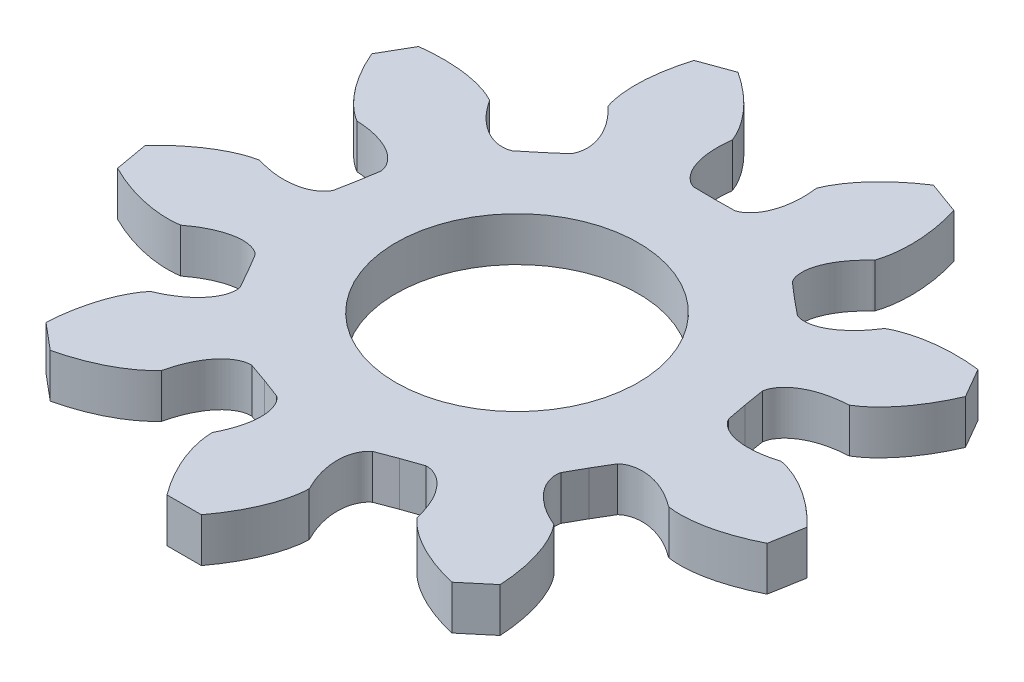
SolidWorks part; units mm, degrees
ref_plane "Plano frontal" through (0, 0, 0) normal (0, 0, 1) x (1, 0, 0)
ref_plane "Plano superior" through (0, 0, 0) normal (0, 1, 0) x (1, 0, 0)
ref_plane "Plano direito" through (0, 0, 0) normal (1, 0, 0) x (0, 0, -1)
sketch "Esboço1" plane through (0, 0, 0) normal (0, 1, 0) x (1, 0, 0)
  line L0 (-25.3837, 16.4538) -> (-26.9413, 13.7561)
  line L1 (-30.0214, -3.712) -> (-29.4805, -6.7798)
  line L2 (-16.4467, -7.3117) -> (-15.4802, -8.9375)
  line L3 (-15.4802, -8.9375) -> (-14.5555, -10.5874)
  line L4 (-17.2988, 4.9706) -> (-17.6034, 3.104)
  line L5 (-17.6034, 3.104) -> (-17.9556, 1.2457)
  line L6 (-8.8688, 28.9207) -> (-11.796, 27.8553)
  line L7 (-10.0566, 14.9272) -> (-11.4898, 13.693)
  line L8 (-11.4898, 13.693) -> (-12.9541, 12.4959)
  line L9 (11.796, 27.8553) -> (8.8688, 28.9207)
  line L10 (1.8912, 17.8991) -> (0, 17.875)
  line L11 (0, 17.875) -> (-1.8912, 17.8991)
  line L12 (26.9413, 13.7561) -> (25.3837, 16.4538)
  line L13 (12.9541, 12.4959) -> (11.4898, 13.693)
  line L14 (11.4898, 13.693) -> (10.0566, 14.9272)
  line L15 (29.4805, -6.7798) -> (30.0214, -3.712)
  line L16 (17.9556, 1.2457) -> (17.6034, 3.104)
  line L17 (17.6034, 3.104) -> (17.2988, 4.9706)
  line L18 (18.2254, -24.1433) -> (20.6117, -22.1409)
  line L19 (14.5555, -10.5874) -> (15.4802, -8.9375)
  line L20 (15.4802, -8.9375) -> (16.4467, -7.3117)
  line L21 (-1.5575, -30.2099) -> (1.5575, -30.2099)
  line L22 (4.3447, -17.4665) -> (6.1136, -16.797)
  line L23 (6.1136, -16.797) -> (7.899, -16.1728)
  line L24 (-20.6117, -22.1409) -> (-18.2254, -24.1433)
  line L25 (-7.899, -16.1728) -> (-6.1136, -16.797)
  line L26 (-6.1136, -16.797) -> (-4.3447, -17.4665)
  circle A1 centre (0, 0) radius 11
  spline S0 degree 3 number of poles 364 (-17.9556, 1.2457) -> (-23.6894, 0.2967)
  spline S1 degree 3 number of poles 420 (-23.6894, 0.2967) -> (-30.0214, -3.712)
  spline S2 degree 3 number of poles 364 (-22.1593, -8.381) -> (-16.4467, -7.3117)
  spline S3 degree 3 number of poles 420 (-29.4805, -6.7798) -> (-22.1593, -8.381)
  spline S4 degree 3 number of poles 420 (-17.9564, 15.4545) -> (-25.3837, 16.4538)
  spline S5 degree 3 number of poles 420 (-26.9413, 13.7561) -> (-22.3622, 7.8235)
  spline S6 degree 3 number of poles 364 (-22.3622, 7.8235) -> (-17.2988, 4.9706)
  spline S7 degree 3 number of poles 364 (-12.9541, 12.4959) -> (-17.9564, 15.4545)
  spline S8 degree 3 number of poles 420 (-3.8215, 23.381) -> (-8.8688, 28.9207)
  spline S9 degree 3 number of poles 420 (-11.796, 27.8553) -> (-12.1016, 20.3673)
  spline S10 degree 3 number of poles 364 (-12.1016, 20.3673) -> (-10.0566, 14.9272)
  spline S11 degree 3 number of poles 364 (-1.8912, 17.8991) -> (-3.8215, 23.381)
  spline S12 degree 3 number of poles 420 (12.1016, 20.3673) -> (11.796, 27.8553)
  spline S13 degree 3 number of poles 420 (8.8688, 28.9207) -> (3.8215, 23.381)
  spline S14 degree 3 number of poles 364 (3.8215, 23.381) -> (1.8912, 17.8991)
  spline S15 degree 3 number of poles 364 (10.0566, 14.9272) -> (12.1016, 20.3673)
  spline S16 degree 3 number of poles 420 (22.3622, 7.8235) -> (26.9413, 13.7561)
  spline S17 degree 3 number of poles 420 (25.3837, 16.4538) -> (17.9564, 15.4545)
  spline S18 degree 3 number of poles 364 (17.9564, 15.4545) -> (12.9541, 12.4959)
  spline S19 degree 3 number of poles 364 (17.2988, 4.9706) -> (22.3622, 7.8235)
  spline S20 degree 3 number of poles 420 (22.1593, -8.381) -> (29.4805, -6.7798)
  spline S21 degree 3 number of poles 420 (30.0214, -3.712) -> (23.6894, 0.2967)
  spline S22 degree 3 number of poles 364 (23.6894, 0.2967) -> (17.9556, 1.2457)
  spline S23 degree 3 number of poles 364 (16.4467, -7.3117) -> (22.1593, -8.381)
  spline S24 degree 3 number of poles 420 (11.5878, -20.6639) -> (18.2254, -24.1433)
  spline S25 degree 3 number of poles 420 (20.6117, -22.1409) -> (18.3378, -15)
  spline S26 degree 3 number of poles 364 (18.3378, -15) -> (14.5555, -10.5874)
  spline S27 degree 3 number of poles 364 (7.899, -16.1728) -> (11.5878, -20.6639)
  spline S28 degree 3 number of poles 420 (-4.4058, -23.278) -> (-1.5575, -30.2099)
  spline S29 degree 3 number of poles 420 (1.5575, -30.2099) -> (4.4058, -23.278)
  spline S30 degree 3 number of poles 364 (4.4058, -23.278) -> (4.3447, -17.4665)
  spline S31 degree 3 number of poles 364 (-4.3447, -17.4665) -> (-4.4058, -23.278)
  spline S32 degree 3 number of poles 420 (-18.3378, -15) -> (-20.6117, -22.1409)
  spline S33 degree 3 number of poles 420 (-18.2254, -24.1433) -> (-11.5878, -20.6639)
  spline S34 degree 3 number of poles 364 (-11.5878, -20.6639) -> (-7.899, -16.1728)
  spline S35 degree 3 number of poles 364 (-14.5555, -10.5874) -> (-18.3378, -15)
  point P77 (0, 0)
  dimension "D1" = 9
extrude "Ressalto-extrusão1" add sketch "Esboço1" along normal blind 4
